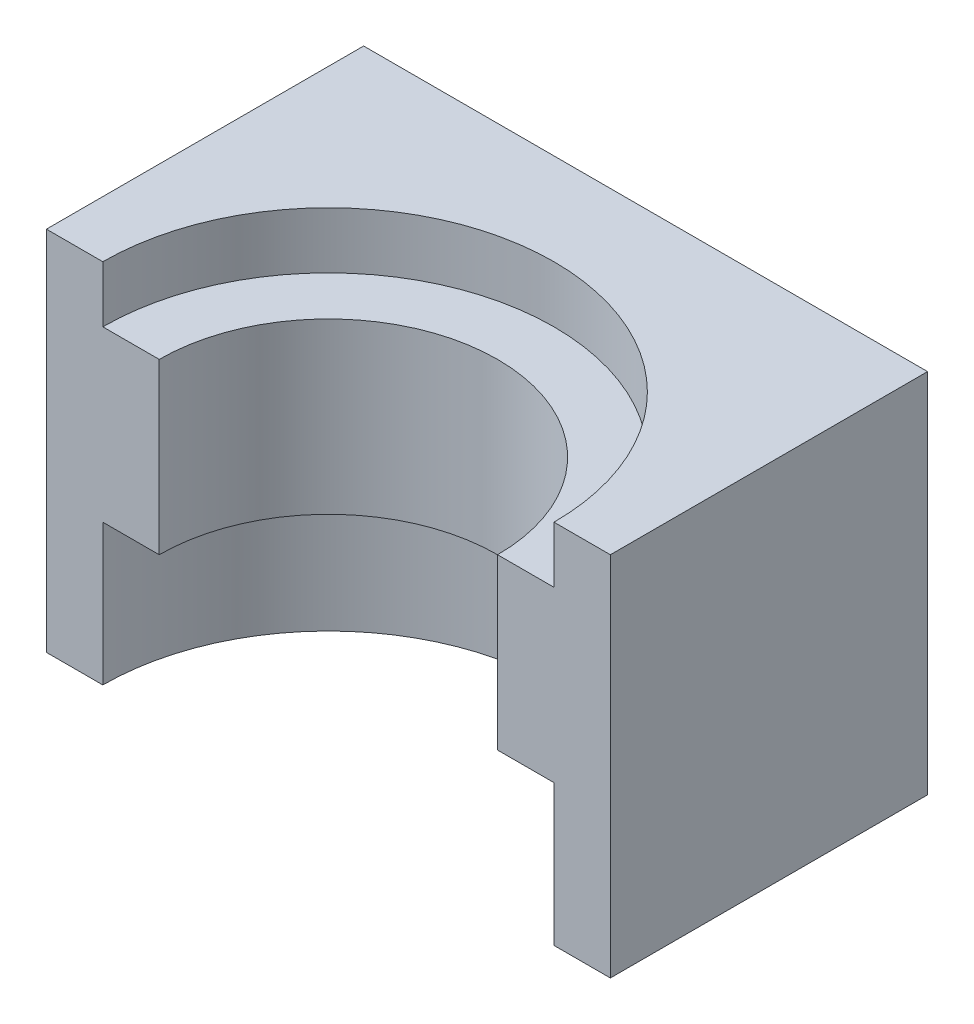
SolidWorks part; units mm, degrees
ref_plane "前视基准面" through (0, 0, 0) normal (0, 0, 1) x (1, 0, 0)
ref_plane "上视基准面" through (0, 0, 0) normal (0, 1, 0) x (1, 0, 0)
ref_plane "右视基准面" through (0, 0, 0) normal (1, 0, 0) x (0, 0, -1)
other "Configuration Table"
sketch "草图1" plane through (0, 0, 0) normal (0, 1, 0) x (1, 0, 0)
  line L0 (0, 8.75) -> (2, 8.75)
  line L2 (0, 8.75) -> (0, 20)
  line L3 (0, 20) -> (20, 20)
  line L4 (20, 8.75) -> (20, 20)
  line L5 (18, 8.75) -> (20, 8.75)
  arc A0 (18, 8.75) -> (2, 8.75) centre (10, 8.75) ccw
  dimension "D3" = 16
  dimension "D1" = 20
  dimension "D2" = 11.25
  dimension "D4" = 10
  dimension "D5" = 11.25
extrude "凸台-拉伸1" add sketch "草图1" along normal blind 5
sketch "草图2" plane through (0, 5, 0) normal (0, 1, 0) x (1, 0, 0)
  line L0 (16, 8.75) -> (20, 8.75)
  line L1 (0, 20) -> (20, 20)
  line L2 (0, 20) -> (0, 8.75)
  line L3 (0, 8.75) -> (4, 8.75)
  line L4 (20, 20) -> (20, 8.75)
  arc A0 (16, 8.75) -> (4, 8.75) centre (10, 8.75) ccw
  dimension "D1" = 12
extrude "凸台-拉伸2" add sketch "草图2" along normal blind 6
sketch "草图3" plane through (0, 11, 0) normal (0, 1, 0) x (1, 0, 0)
  line L0 (18, 8.75) -> (20, 8.75)
  line L1 (0, 20) -> (20, 20)
  line L2 (0, 20) -> (0, 8.75)
  line L3 (0, 8.75) -> (2, 8.75)
  line L4 (20, 20) -> (20, 8.75)
  arc A0 (18, 8.75) -> (2, 8.75) centre (10, 8.75) ccw
  dimension "D1" = 16
extrude "凸台-拉伸3" add sketch "草图3" along normal blind 2
sketch "草图4" plane through (0, 0, -20) normal (0, 0, -1) x (-1, 0, 0)
  line L0 (-20, 0) -> (0, 0) construction
  circle A0 centre (-13.5, -13) radius 13.5
  point P4 (-10, 0)
  point P6 (-48.5142, 25.9595)
  dimension "D2" = 3.5
  dimension "D3" = 27
  dimension "D1" = 13
extrude "切除-拉伸1" cut sketch "草图4" against normal blind 4
equation "\"D2@草图1\"=22.5/2"
equation "\"D5@草图1\"=\"D2@草图1\""
